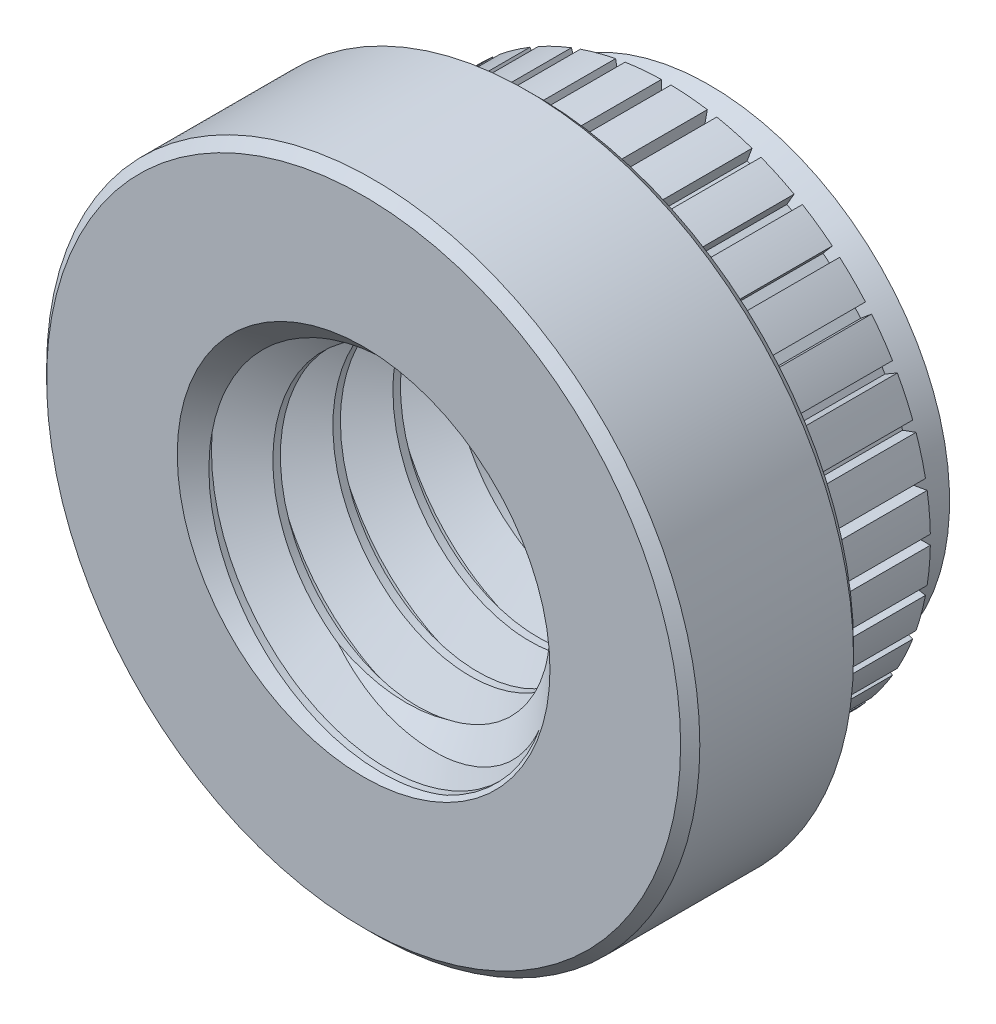
SolidWorks part; units mm, degrees
ref_plane "Front Plane" through (0, 0, 0) normal (0, 0, 1) x (1, 0, 0)
ref_plane "Top Plane" through (0, 0, 0) normal (0, 1, 0) x (1, 0, 0)
ref_plane "Right Plane" through (0, 0, 0) normal (1, 0, 0) x (0, 0, -1)
sketch "Sketch1" plane through (0, 0, 0) normal (0, 0, 1) x (1, 0, 0)
  circle A0 centre (0, 0) radius 4.318
  dimension "A" = 8.636
extrude "Extrude1" add sketch "Sketch1" against normal blind 2.286
sketch "Sketch15" plane through (0, 0, -2.286) normal (0, 0, -1) x (-1, 0, 0)
  circle A0 centre (0, 0) radius 3.175
  dimension "hole dia" = 6.35
sketch "Sketch2" plane through (0, 0, -2.286) normal (0, 0, -1) x (-1, 0, 0)
  circle A0 centre (0, 0) radius 3.4925
  dimension "D1" = 6.985
extrude "Extrude2" add sketch "Sketch2" along normal blind 2.286
sketch "Sketch3" plane through (0, 0, -4.572) normal (0, 0, -1) x (-1, 0, 0)
  line L0 (0, 3.302) -> (0, 4.318)
  circle A1 centre (0, 0) radius 4.318 construction
  circle A2 centre (0, 0) radius 3.302
  circle A3 centre (0, 0) radius 3.302 construction
  dimension "D1" = 0.1905
extrude "Cut-Extrude-Thin1" cut sketch "Sketch3" against normal up to surface (2.286 mm away) thin up to face at (4.318, 0, -2.286) thin type mid plane wall 0.127
pattern_circular "CirPattern1" count 36 over 360 about axis through (0, 0, 0) along (0, 0, 1) of "Cut-Extrude-Thin1"
sketch "Sketch5" plane through (0, 0, -4.572) normal (0, 0, -1) x (-1, 0, 0)
  circle A0 centre (0, 0) radius 4.318 construction
  circle A3 centre (0, 0) radius 3.175
  dimension "C" = 6.35
extrude "Cut-Extrude1" cut sketch "Sketch5" against normal blind 0.5715 draft 20 flip side to cut draft outward yes
chamfer "Chamfer2" distance 0.127 angle 45 2 edges at (4.318, 0, 0) (4.318, 0, -2.286)
sketch "Sketch7" plane through (0, 0, 0) normal (0, 0, 1) x (1, 0, 0)
  circle A0 centre (0, 0) radius 2.413
  dimension "Thread Od" = 4.826
extrude "Cut-Extrude3" cut sketch "Sketch7" against normal through all
sketch "Sketch8" plane through (0, 0, -4.572) normal (0, 0, -1) x (-1, 0, 0)
  circle A0 centre (0, 0) radius 2.413 construction
  circle A1 centre (0, 0) radius 2.413
curve "Helix/Spiral1" pitch 0.7937 height 7.747 turns 9.76 parameters "pitch"=0.7937
sketch "Sketch9" plane through (0, 0, 0) normal (1, 0, 0) x (0, 0, -1)
  line L0 (5.2665, 2.413) -> (4.9689, 1.8974)
  line L1 (4.9689, 1.8974) -> (4.8697, 1.8974)
  line L2 (4.8697, 1.8974) -> (4.572, 2.413)
  line L3 (5.2665, 2.413) -> (4.572, 2.413)
  line L4 (4.9193, 2.413) -> (4.9193, 1.8974) construction
  line L5 (5.1177, 2.1552) -> (4.7208, 2.1552) construction
  line L6 (4.572, -2.413) -> (4.572, 2.413) construction
  dimension "D1" = 60
  dimension "D2" = 0.0992
  dimension "D3" = 0.3969
sweep "Sweep1" add profiles "Sketch9" path "Helix/Spiral1"
sketch "Sketch10" plane through (0, 0, 0) normal (0, 0, 1) x (1, 0, 0)
  circle A0 centre (0, 0) radius 4.318 construction
  circle A1 centre (0, 0) radius 4.318
extrude "Cut-Extrude4" cut sketch "Sketch10" along normal through all
sketch "Sketch11" plane through (0, 0, -4.572) normal (0, 0, -1) x (-1, 0, 0)
  circle A1 centre (0, 0) radius 3.175 construction
  circle A2 centre (0, 0) radius 3.175
extrude "Cut-Extrude5" cut sketch "Sketch11" along normal through all
sketch "Sketch13" plane through (0, 0, 0) normal (0, 0, 1) x (1, 0, 0)
  circle A2 centre (0, 0) radius 2.4638
  circle A3 centre (0, 0) radius 2.4638
  dimension "D1" = 0.0508
extrude "Cut-Extrude6" cut sketch "Sketch13" against normal through all draft 45
sketch "Sketch14" plane through (0, 0, -4.572) normal (0, 0, -1) x (-1, 0, 0)
  circle A2 centre (0, 0) radius 2.4638
  circle A3 centre (0, 0) radius 2.4638
  dimension "D1" = 0.0508
extrude "Cut-Extrude7" cut sketch "Sketch14" against normal through all draft 45
equation "\"D3@Helix/Spiral1\" = \"B@Extrude1\"+\"panel min.@Extrude2\"+.125"
equation "\"D2@Sketch9\" = \"pitch@Helix/Spiral1\"*.125"
equation "\"D3@Sketch9\" = \"pitch@Helix/Spiral1\"*.50"
equation "\"D1@Sketch2\" = \"hole dia@Sketch15\"+.025"
equation "\"D1@Cut-Extrude1\" = \"panel min.@Extrude2\"*.25"
